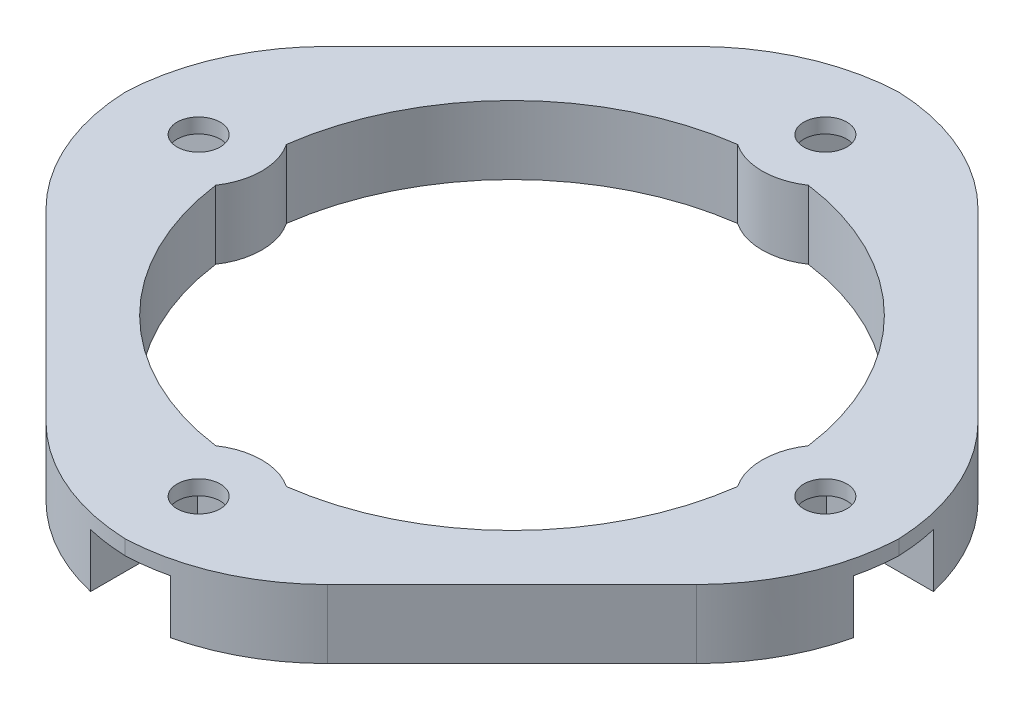
SolidWorks part; units mm, degrees
ref_plane "Спереди" through (0, 0, 0) normal (0, 0, 1) x (1, 0, 0)
ref_plane "Сверху" through (0, 0, 0) normal (0, 1, 0) x (1, 0, 0)
ref_plane "Справа" through (0, 0, 0) normal (1, 0, 0) x (0, 0, -1)
sketch "Sketch1" plane through (0, 0, 0) normal (0, 1, 0) x (1, 0, 0)
  circle A0 centre (0, 0) radius 75
  circle A1 centre (0, 0) radius 50
  dimension "D1" = 150
  dimension "D2" = 100
extrude "Boss-Extrude1" add sketch "Sketch1" along normal blind 13
sketch "Sketch2" plane through (0, 13, 0) normal (0, 1, 0) x (1, 0, 0)
  line L0 (0, 75) -> (0, -75) construction
  line L1 (-75, 0) -> (75, 0) construction
  circle A0 centre (0, 0) radius 75 construction
  circle A1 centre (0, 59.5) radius 4.1
  circle A2 centre (59.5, 0) radius 4.1
  circle A3 centre (0, -59.5) radius 4.1
  circle A4 centre (-59.5, 0) radius 4.1
  circle A5 centre (0, 0) radius 59.5 construction
  point P17 (0, -60.5334)
  point P19 (0, 0)
  point P20 (0, 0)
  point P21 (0, 0)
  point P22 (0, 0)
  point P23 (0, 0)
  point P24 (0, 0)
  dimension "D1" = 8.2
  dimension "D2" = 119
extrude "Cut-Extrude1" cut sketch "Sketch2" against normal through all
sketch "Sketch8" plane through (0, 13, 0) normal (0, 1, 0) x (1, 0, 0)
  circle A0 centre (59.5, 0) radius 12
  circle A1 centre (0, -59.5) radius 12
  circle A2 centre (-59.5, 0) radius 12
  circle A3 centre (0, 59.5) radius 12
  circle A4 centre (0, 59.5) radius 4.1
  circle A5 centre (59.5, 0) radius 4.1
  circle A6 centre (0, -59.5) radius 4.1
  circle A7 centre (-59.5, 0) radius 4.1
  circle A8 centre (-59.5, 0) radius 4.1 construction
  dimension "D1" = 24
extrude "Boss-Extrude4" add sketch "Sketch8" against normal up to surface (13 mm away) up to face at (59.5, 0, 4.1)
sketch "Sketch3" plane through (0, 0, 0) normal (0, -1, 0) x (1, 0, 0)
  line L0 (-35.7148, 0) -> (-75, 0) construction
  line L1 (7.6, 52.1) -> (-7.6, 52.1)
  line L2 (7.6, 52.1) -> (7.6, 92.1)
  line L3 (7.6, 92.1) -> (-7.6, 92.1)
  line L4 (-7.6, 52.1) -> (-7.6, 92.1)
  line L5 (7.6, 52.1) -> (-7.6, 92.1) construction
  line L6 (7.6, 92.1) -> (-7.6, 52.1) construction
  line L7 (92.1, -7.6) -> (52.1, -7.6)
  line L8 (92.1, -7.6) -> (92.1, 7.6)
  line L9 (92.1, 7.6) -> (52.1, 7.6)
  line L10 (52.1, -7.6) -> (52.1, 7.6)
  line L11 (92.1, -7.6) -> (52.1, 7.6) construction
  line L12 (92.1, 7.6) -> (52.1, -7.6) construction
  line L13 (7.6, -92.1) -> (-7.6, -92.1)
  line L14 (7.6, -92.1) -> (7.6, -52.1)
  line L15 (7.6, -52.1) -> (-7.6, -52.1)
  line L16 (-7.6, -92.1) -> (-7.6, -52.1)
  line L17 (7.6, -92.1) -> (-7.6, -52.1) construction
  line L18 (7.6, -52.1) -> (-7.6, -92.1) construction
  line L19 (-52.1, -7.6) -> (-92.1, -7.6)
  line L20 (-52.1, -7.6) -> (-52.1, 7.6)
  line L21 (-52.1, 7.6) -> (-92.1, 7.6)
  line L22 (-92.1, -7.6) -> (-92.1, 7.6)
  line L23 (-52.1, -7.6) -> (-92.1, 7.6) construction
  line L24 (-52.1, 7.6) -> (-92.1, -7.6) construction
  line L25 (0, -47.5) -> (0, -75) construction
  line L26 (47.5, 0) -> (75, 0) construction
  line L27 (0, 47.5) -> (0, 59.5) construction
  line L28 (0, 59.5) -> (0, 75) construction
  circle A0 centre (0, 0) radius 75 construction
  arc A1 (6.7055, -49.5483) -> (-6.7055, -49.5483) centre (0, -59.5) ccw construction
  arc A2 (49.5483, 6.7055) -> (49.5483, -6.7055) centre (59.5, 0) ccw construction
  arc A3 (-6.7055, 49.5483) -> (6.7055, 49.5483) centre (0, 59.5) ccw construction
  circle A4 centre (0, 0) radius 72.1 construction
  point P0 (0, 72.1)
  point P6 (72.1, 0)
  point P12 (0, -72.1)
  point P18 (-72.1, 0)
  dimension "D1" = 15.2
  dimension "D2" = 7.4
  dimension "D3" = 40
extrude "Cut-Extrude2" cut sketch "Sketch3" against normal blind 10.2
sketch "Sketch4" plane through (0, 13, 0) normal (0, 1, 0) x (1, 0, 0)
  line L0 (0, 0) -> (-53.033, -53.033) construction
  line L1 (0, 0) -> (0, -75) construction
  line L2 (-40.6586, -65.4074) -> (-65.4074, -40.6586)
  line L3 (-65.4074, -40.6586) -> (-63.9435, -39.1948)
  line L4 (-63.9435, -39.1948) -> (-39.1948, -63.9435)
  line L5 (-39.1948, -63.9435) -> (-40.6586, -65.4074)
  circle A0 centre (0, 0) radius 75 construction
  point P10 (-53.033, -53.033)
  dimension "D1" = 45
  dimension "D2" = 35
extrude "Boss-Extrude2" add sketch "Sketch4" against normal up to surface (13 mm away) up to face at (0, 0, 0)
fillet "Fillet1" radius 30 2 edges at (-63.9435, 6.5, 39.1948) (-39.1948, 6.5, 63.9435)
sketch "Sketch7" plane through (0, 13, 0) normal (0, 1, 0) x (1, 0, 0)
  line L0 (73.4847, -15) -> (15, -73.4847)
  line L1 (15, -73.4847) -> (-15, -73.4847)
  line L2 (-15, -73.4847) -> (-73.4847, -15)
  line L3 (-73.4847, -15) -> (-73.4847, 15)
  line L4 (-73.4847, 15) -> (-15, 73.4847)
  line L5 (-15, 73.4847) -> (15, 73.4847)
  line L6 (15, 73.4847) -> (73.4847, 15)
  line L7 (73.4847, 15) -> (73.4847, -15)
  line L8 (59.5, 0) -> (0, 0) construction
  line L9 (59.5, 0) -> (73.4847, 0) construction
  arc A0 (-31.6671, -67.9867) -> (-67.9867, -31.6671) centre (0, 0) ccw construction
  arc A1 (-31.6671, -67.9867) -> (-67.9867, -31.6671) centre (0, 0) ccw construction
  dimension "D1" = 30
extrude "Cut-Extrude4" cut sketch "Sketch7" against normal through all flip side to cut
fillet "Fillet3" radius 40 8 edges at (15, 6.5, 73.4847) (-15, 6.5, 73.4847) (-73.4847, 6.5, 15) (-73.4847, 6.5, -15) (-15, 6.5, -73.4847) (15, 6.5, -73.4847) (73.4847, 6.5, 15) (73.4847, 6.5, -15)
